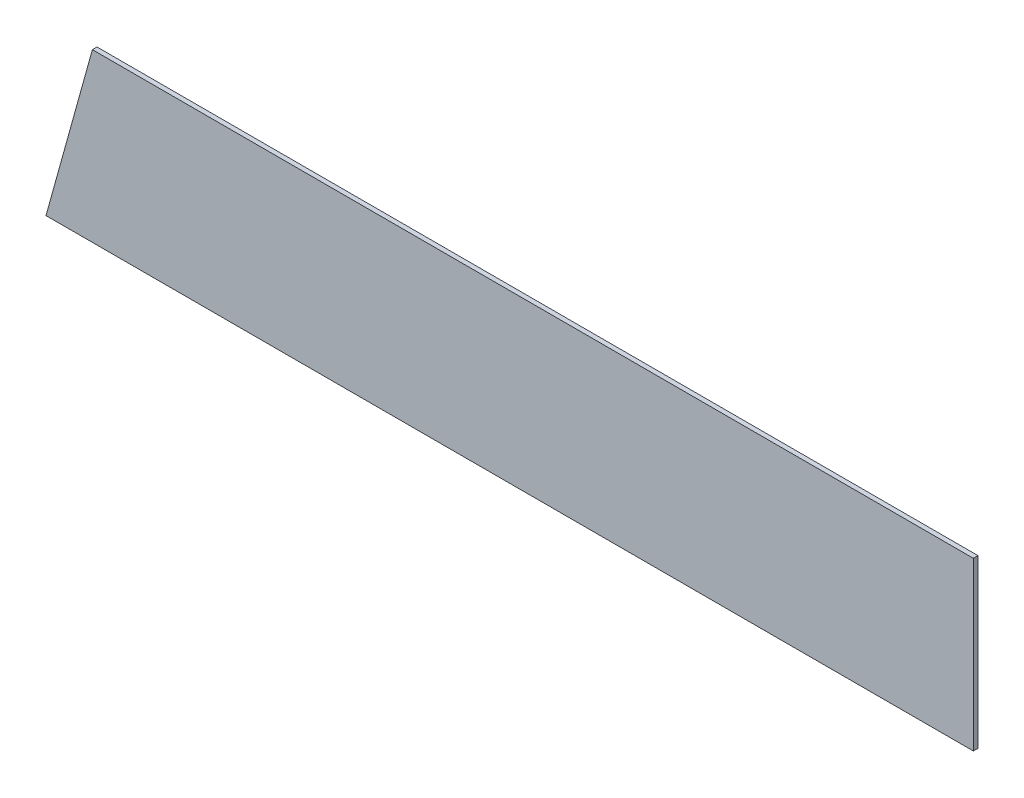
SolidWorks part; units mm, degrees
material "AISI Type A2 Tool Steel"
ref_plane "Front Plane" through (0, 0, 0) normal (0, 0, 1) x (1, 0, 0)
ref_plane "Top Plane" through (0, 0, 0) normal (0, 1, 0) x (1, 0, 0)
ref_plane "Right Plane" through (0, 0, 0) normal (1, 0, 0) x (0, 0, -1)
sketch "Croquis1" plane through (0, 0, 0) normal (0, 0, 1) x (1, 0, 0)
  line L1 (-40.9906, 8.2783) -> (54.0094, 8.2783)
  line L6 (54.0094, 8.2783) -> (54.0094, -9.7217)
  line L7 (54.0094, -9.7217) -> (-45.9906, -9.7217)
  line L8 (-40.9906, 8.2783) -> (-45.9906, -9.7217)
  point P0 (0, 0)
  dimension "D1" = 5
  dimension "D2" = 18
  dimension "D3" = 100
extrude "Saliente-Extruir1" add sketch "Croquis1" along normal blind 0.5
